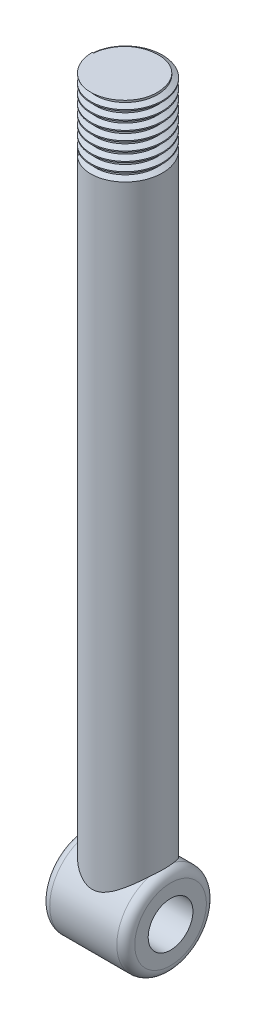
SolidWorks part; units mm, degrees
other "DetailItem1"
other "Weld Folder"
other "Weld Bead1"
material "6061 Alloy"
ref_plane "Front Plane" through (0, 0, 0) normal (0, 0, 1) x (1, 0, 0)
ref_plane "Top Plane" through (0, 0, 0) normal (0, 1, 0) x (1, 0, 0)
ref_plane "Right Plane" through (0, 0, 0) normal (1, 0, 0) x (0, 0, -1)
sketch "Sketch1" plane through (0, 0, 0) normal (0, 1, 0) x (1, 0, 0)
  line L0 (-6.0325, 3.175) -> (-6.0325, 6.35)
  line L1 (-6.0325, -3.175) -> (6.0325, -3.175) construction
  line L2 (-6.0325, -3.175) -> (-6.0325, 3.175) construction
  line L3 (-6.0325, 3.175) -> (6.0325, 3.175)
  line L4 (6.0325, -3.175) -> (6.0325, 3.175) construction
  line L5 (-6.0325, -3.175) -> (6.0325, 3.175) construction
  line L6 (-6.0325, 3.175) -> (6.0325, -3.175) construction
  line L7 (-6.0325, 6.35) -> (6.0325, 6.35)
  line L8 (6.0325, 6.35) -> (6.0325, 3.175)
  line L9 (0, 0) -> (6.0325, 0) construction
  point P0 (0, 0)
  dimension "D1" = 12.065
  dimension "D2" = 6.35
  dimension "D3" = 3.175
revolve "Revolve1" add sketch "Sketch1" angle 360 about L9
fillet "Fillet1" radius 1.27 2 edges at (-6.0325, 0, 6.35) (6.0325, 0, 6.35)
ref_plane "Plane1" through (0, 6.35, 0) normal (0, 1, 0) x (1, 0, 0)
sketch "Sketch2" plane through (0, 6.35, 0) normal (0, 1, 0) x (1, 0, 0)
  circle A0 centre (0, 0) radius 5.08
  dimension "D1" = 10.16
extrude "Boss-Extrude1" add sketch "Sketch2" along normal blind 95.25 and the other way blind 2.54 separate body
thread "Thread1" pitch 1.27 method cut profile "Thread Profile1" start angle 0, offset 1, length 10, pitch 1.27, diameter 10.16
ref_plane "Plane2" through (-5.08, 102.6, 0) normal (0, 0, 1) x (-1, 0, 0)
sketch "Thread Profile1" plane through (-5.08, 102.6, 0) normal (0, 0, 1) x (-1, 0, 0)
  line L0 (0, 0) -> (0, 1.27) construction
  line L11 (0, 0) -> (0, 1.1112)
  line L12 (0, 1.1112) -> (-0.6874, 0.7144)
  line L13 (-0.6874, 0.7144) -> (-0.6874, 0.3969)
  line L15 (-0.6874, 0.3969) -> (0, 0)
  line L17 (-0.6874, 0.5556) -> (0, 0.5556) construction
  point P2 (0, 0)
  dimension "Pitch" = 1.27
  dimension "Profile_Angle" = 60
  dimension "Profile_Land" = 0.3175
  dimension "Profile_Height" = 0.6874
